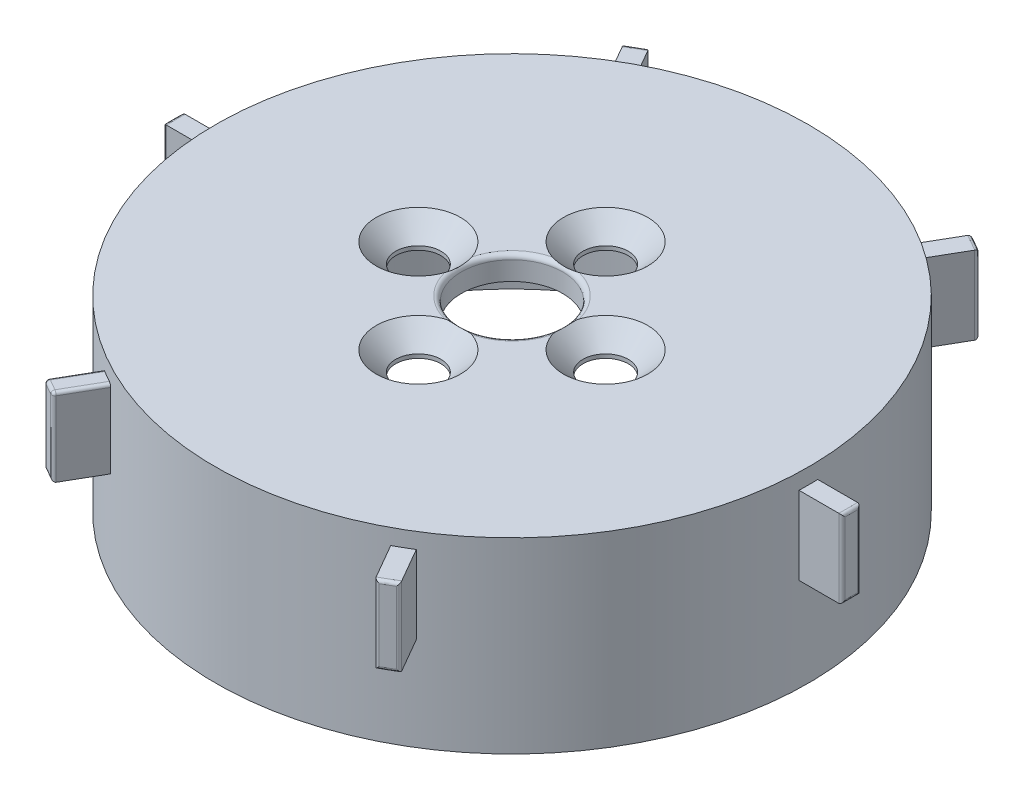
SolidWorks part; units mm, degrees
ref_plane "前视基准面" through (0, 0, 0) normal (0, 0, 1) x (1, 0, 0)
ref_plane "上视基准面" through (0, 0, 0) normal (0, 1, 0) x (1, 0, 0)
ref_plane "右视基准面" through (0, 0, 0) normal (1, 0, 0) x (0, 0, -1)
sketch "草图2" plane through (0, 0, 0) normal (0, 0, 1) x (1, 0, 0)
  line L0 (0, 0) -> (0, 24.3345) construction
  line L1 (-17.5, 0) -> (-17.5, 10.5)
  line L2 (-17.5, 10.5) -> (-3.25, 10.5)
  line L3 (-3.25, 10.5) -> (-3.25, 12)
  line L4 (-3.25, 12) -> (-19, 12)
  line L5 (-19, 12) -> (-19, 0)
  line L6 (-19, 0) -> (-17.5, 0)
  dimension "D1" = 1.5
  dimension "D2" = 1.5
  dimension "D3" = 35
  dimension "D4" = 6.5
  dimension "D5" = 10.5
revolve "旋转1" add sketch "草图2" angle 360 about L0
sketch "草图4" plane through (0, 12, 0) normal (0, 1, 0) x (1, 0, 0)
  line L0 (-28.2482, 0) -> (28.2482, 0) construction
  line L1 (0, 25.6778) -> (0, -25.6778) construction
  point P0 (-6, 0)
  point P4 (0, 0)
  point P8 (0, 0)
  point P9 (0, 6)
  point P10 (6, 0)
  point P11 (0, -6)
  dimension "D1" = 12
  dimension "D2" = 12
hole_wizard "打孔尺寸(%根据十字)槽半沉头木螺钉的类型0" positions "草图5" profile "草图6" countersink size "M2.5" standard "GB" end condition through all
sketch "草图5" plane through (0, 12, 0) normal (0, 1, 0) x (1, 0, 0)
  point P0 (-6, 0)
  point P3 (0, 6)
  point P6 (6, 0)
  point P9 (0, -6)
sketch "草图6" plane through (-6, 12, 0) normal (1, 0, 0) x (0, 0, 1)
  line L0 (0, 0) -> (0, 12)
  line L1 (0, 12) -> (1.45, 12)
  line L2 (1.45, 12) -> (1.45, 1.25)
  line L3 (1.45, 1.25) -> (2.7, 0)
  line L5 (2.7, 0) -> (0, 0)
  line L6 (-1.45, 1.25) -> (-2.7, 0) construction
  line L11 (0, -6.35) -> (0, 107.95) construction
  dimension "通孔孔直径" = 2.9
  dimension "通孔孔深度" = 12
  dimension "近端锥形沉头孔直径" = 5.4
  dimension "近端锥形沉头孔角度" = 90
sketch "草图9" plane through (0, 12, 0) normal (0, 1, 0) x (1, 0, 0)
  line L0 (0, 0) -> (-30.5241, 0) construction
  line L1 (-25, 0.6) -> (-25, -0.6)
  line L2 (-25, -0.6) -> (-18.9905, -0.6)
  line L3 (-25, 0.6) -> (-18.9905, 0.6)
  line L4 (-11.9804, 21.9506) -> (-13.0196, 21.3506)
  line L5 (-13.0196, 21.3506) -> (-10.0149, 16.1463)
  line L6 (-11.9804, 21.9506) -> (-8.9756, 16.7463)
  line L7 (13.0196, 21.3506) -> (11.9804, 21.9506)
  line L8 (11.9804, 21.9506) -> (8.9756, 16.7463)
  line L9 (13.0196, 21.3506) -> (10.0149, 16.1463)
  line L10 (25, -0.6) -> (25, 0.6)
  line L11 (25, 0.6) -> (18.9905, 0.6)
  line L12 (25, -0.6) -> (18.9905, -0.6)
  line L13 (11.9804, -21.9506) -> (13.0196, -21.3506)
  line L14 (13.0196, -21.3506) -> (10.0149, -16.1463)
  line L15 (11.9804, -21.9506) -> (8.9756, -16.7463)
  line L16 (-13.0196, -21.3506) -> (-11.9804, -21.9506)
  line L17 (-11.9804, -21.9506) -> (-8.9756, -16.7463)
  line L18 (-13.0196, -21.3506) -> (-10.0149, -16.1463)
  circle A1 centre (0, 0) radius 19
  circle A2 centre (0, 0) radius 19
  dimension "D2" = 1.2
  dimension "D3" = 25
  dimension "D1" = 0
  dimension "D4" = 6
extrude "凸台-拉伸3" add sketch "草图9" against normal blind 5 from offset 1 contours L18 L16 L17 L6 | L15 L13 L14 L6 | L12 L10 L11 L6 | L9 L7 L8 L6 | L6 L4 L5 | A2 L0 L1 L2 | L0 L6 L3 L1 offset against normal yes
sketch "草图10" plane through (0, 12, 0) normal (0, 1, 0) x (1, 0, 0)
  circle A0 centre (0, 0) radius 21.75
  dimension "D1" = 43.5
extrude "切除-拉伸1" cut sketch "草图10" against normal up to next flip side to cut
fillet "圆角2" radius 0.2 26 edges at (-10.3512, 8.5, 19.1289) (-11.3905, 8.5, 18.5289) (-21.7417, 8.5, -0.6) (-21.7417, 8.5, 0.6) (-10.3512, 8.5, -19.1289) (-11.3905, 8.5, -18.5289) (11.3905, 8.5, -18.5289) (10.3512, 8.5, -19.1289) (21.7417, 8.5, -0.6) (21.7417, 8.5, 0.6) (11.3905, 8.5, 18.5289) (10.3512, 8.5, 19.1289) (-10.875, 6, 18.8361) (-21.75, 6, 0) (-21.75, 11, 0) (-10.875, 6, -18.8361) (10.875, 6, -18.8361) (21.75, 6, 0) (10.875, 6, 18.8361) (-10.7027, 11, 17.3376) (-9.6634, 11, 17.9376) (-10.875, 11, 18.8361) (-10.875, 11, -18.8361) (10.875, 11, -18.8361) (21.75, 11, 0) (10.875, 11, 18.8361)
fillet "圆角3" radius 0.3 1 edges at (0, 12, -3.25)
